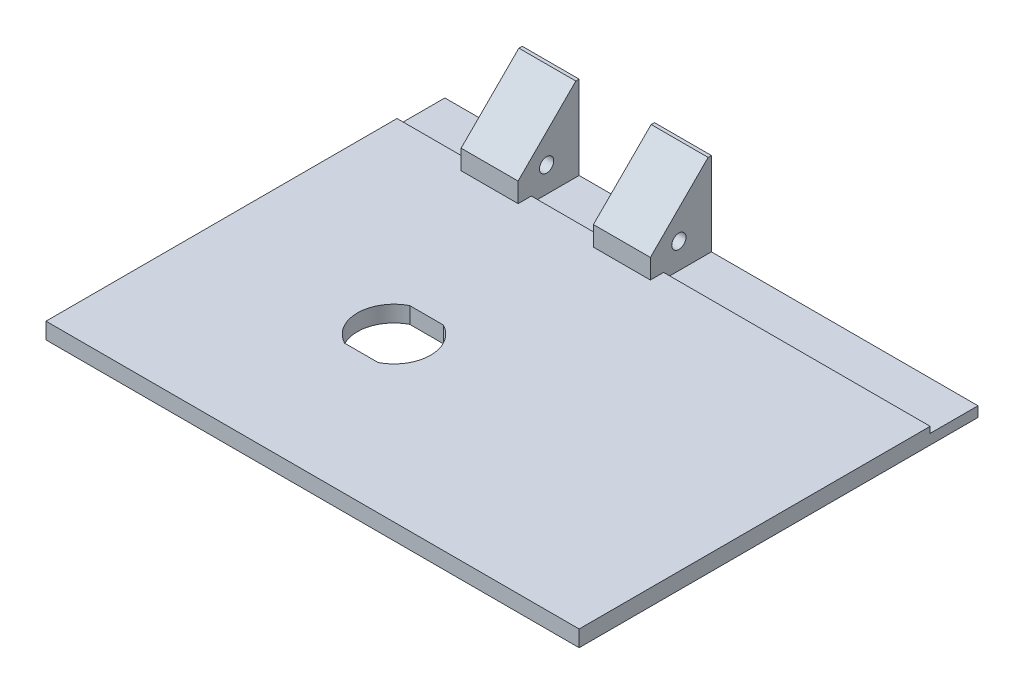
SolidWorks part; units mm, degrees
ref_plane "Ebene vorne" through (0, 0, 0) normal (0, 0, 1) x (1, 0, 0)
ref_plane "Ebene oben" through (0, 0, 0) normal (0, 1, 0) x (1, 0, 0)
ref_plane "Ebene rechts" through (0, 0, 0) normal (1, 0, 0) x (0, 0, -1)
sketch "Sketch1" plane through (0, 0, 0) normal (0, 1, 0) x (1, 0, 0)
  line L1 (65.5, -49) -> (-65.5, -49)
  line L2 (65.5, -49) -> (65.5, 49)
  line L3 (65.5, 49) -> (-65.5, 49)
  line L4 (-65.5, -49) -> (-65.5, 49)
  line L5 (65.5, -49) -> (-65.5, 49) construction
  line L6 (65.5, 49) -> (-65.5, -49) construction
  point P0 (0, 0)
  dimension "D1" = 131
  dimension "D2" = 98
extrude "Boss-Extrude1" add sketch "Sketch1" along normal blind 4
sketch "Lock" plane through (0, 4, 0) normal (0, 1, 0) x (1, 0, 0)
  line L0 (-24.1231, -1) -> (-15.8769, -1)
  line L1 (-24.1231, -17) -> (-15.8769, -17)
  line L2 (-20, -1) -> (-20, -12.568) construction
  line L3 (-65.5, -49) -> (65.5, -49) construction
  line L4 (-20, -45.8205) -> (-20, -27.3505) construction
  arc A0 (-24.1231, -1) -> (-24.1231, -17) centre (-20, -9) ccw
  arc A1 (-15.8769, -17) -> (-15.8769, -1) centre (-20, -9) ccw
  dimension "D1" = 9
  dimension "D3" = 40
  dimension "D2" = 16
  dimension "D4" = 45.5
extrude "Lock Hole" cut sketch "Lock" against normal through all
sketch "Sketch6" plane through (-65.5, 0, 0) normal (-1, 0, 0) x (0, 0, 1)
  line L1 (-49, 4) -> (-37.25, 4)
  line L2 (-49, 4) -> (-49, 2.5)
  line L3 (-49, 2.5) -> (-37.25, 2.5)
  line L4 (-37.25, 4) -> (-37.25, 2.5)
  dimension "D1" = 1.5
  dimension "D2" = 11.75
extrude "Cut-Extrude4" cut sketch "Sketch6" against normal up to surface (131 mm away) up to face at (65.5, 2, 0)
sketch "Sketch3" plane through (0, 4, 0) normal (0, 1, 0) x (1, 0, 0)
  line L0 (65.5, 49) -> (-65.5, 49) construction
  line L1 (-14, 49) -> (0, 49)
  line L2 (-14, 49) -> (-14, 34)
  line L3 (-14, 34) -> (0, 34)
  line L4 (0, 49) -> (0, 34)
  line L6 (65.5, 49) -> (-65.5, 49) construction
  line L7 (-46.5, 49) -> (-32.5, 49)
  line L8 (-46.5, 49) -> (-46.5, 34)
  line L9 (-46.5, 34) -> (-32.5, 34)
  line L10 (-32.5, 49) -> (-32.5, 34)
  dimension "D1" = 15
  dimension "D2" = 14
  dimension "D3" = 14
  dimension "D4" = 18.5
extrude "Boss-Extrude2" add sketch "Sketch3" along normal blind 19
sketch "Sketch4" plane through (-46.5, 0, 0) normal (-1, 0, 0) x (0, 0, 1)
  line L0 (-49, 0) -> (49, 0) construction
  line L3 (-49, 23) -> (-49, 4) construction
  circle A0 centre (-41, 8.75) radius 1.75
  dimension "D1" = 3.5
  dimension "D2" = 8.75
  dimension "D3" = 8
extrude "Cut-Extrude2" cut sketch "Sketch4" against normal through all both and the other way through all
sketch "Sketch5" plane through (-46.5, 0, 0) normal (-1, 0, 0) x (0, 0, 1)
  line L0 (-34, 8.8117) -> (-48.1883, 23)
  line L1 (-34, 23) -> (-34, 4) construction
  line L2 (-49, 23) -> (-34, 23) construction
  line L3 (-48.1883, 23) -> (-34, 23)
  line L4 (-34, 23) -> (-34, 8.8117)
  dimension "D2" = 45
extrude "Cut-Extrude3" cut sketch "Sketch5" against normal through all both and the other way through all
sketch "Sketch8" plane through (0, 0, -49) normal (0, 0, -1) x (-1, 0, 0)
  line L0 (-65.5, 2.5) -> (65.5, 2.5) construction
  line L1 (14, 4) -> (0, 4)
  line L2 (14, 4) -> (14, 2.5)
  line L3 (14, 2.5) -> (0, 2.5)
  line L4 (0, 4) -> (0, 2.5)
  line L6 (46.5, 4) -> (32.5, 4)
  line L7 (46.5, 4) -> (46.5, 2.5)
  line L8 (46.5, 2.5) -> (32.5, 2.5)
  line L9 (32.5, 4) -> (32.5, 2.5)
extrude "Boss-Extrude3" add sketch "Sketch8" against normal up to surface (11.75 mm away) up to face at (-11.625, 3.625, -37.25)
